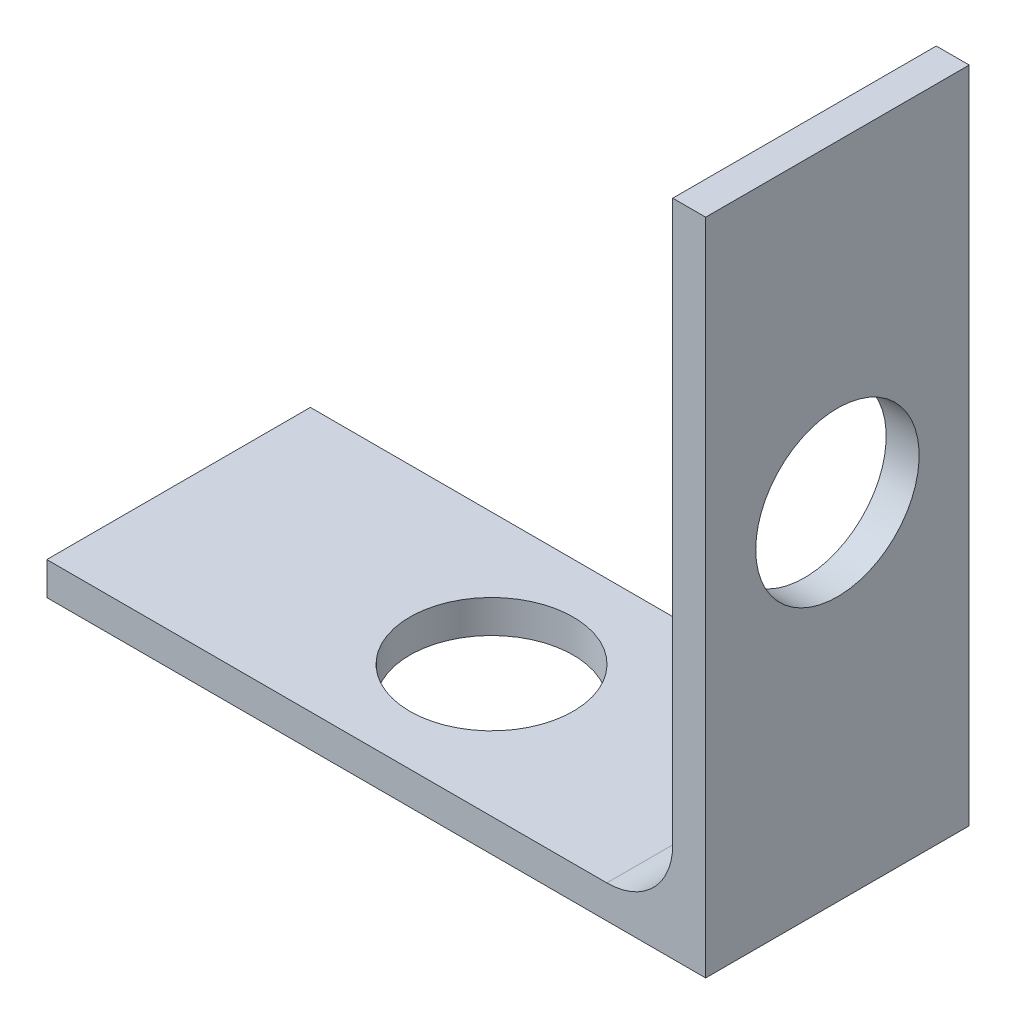
SolidWorks part; units mm, degrees
ref_plane "Front Plane" through (0, 0, 0) normal (0, 0, 1) x (1, 0, 0)
ref_plane "Top Plane" through (0, 0, 0) normal (0, 1, 0) x (1, 0, 0)
ref_plane "Right Plane" through (0, 0, 0) normal (1, 0, 0) x (0, 0, -1)
sketch "Sketch1" plane through (0, 0, 0) normal (0, 0, 1) x (1, 0, 0)
  line L0 (0, 0) -> (31.75, 0)
  line L1 (31.75, 0) -> (31.75, 31.75)
  line L2 (0, 0) -> (0, 1.5875)
  line L3 (0, 1.5875) -> (30.1625, 1.5875)
  line L4 (30.1625, 1.5875) -> (30.1625, 31.75)
  line L5 (30.1625, 31.75) -> (31.75, 31.75)
  dimension "D1" = 31.75
  dimension "D2" = 31.75
  dimension "D3" = 1.5875
  dimension "D4" = 1.5875
extrude "Boss-Extrude1" add sketch "Sketch1" along normal blind 12.7
sketch "Sketch2" plane through (30.1625, 0, 0) normal (-1, 0, 0) x (0, 0, 1)
  line L0 (6.35, 31.75) -> (6.35, 1.5875) construction
  line L1 (12.7, 31.75) -> (0, 31.75) construction
  line L2 (12.7, 1.5875) -> (0, 1.5875) construction
  line L3 (0, 16.6687) -> (12.7, 16.6687) construction
  line L4 (0, 31.75) -> (0, 1.5875) construction
  line L5 (12.7, 31.75) -> (12.7, 1.5875) construction
  circle A0 centre (6.35, 16.6687) radius 3.937
  dimension "D1" = 7.874
extrude "Cut-Extrude1" cut sketch "Sketch2" against normal blind 6.35
sketch "Sketch4" plane through (0, 1.5875, 0) normal (0, 1, 0) x (1, 0, 0)
  line L0 (15.0813, 0) -> (15.0813, -12.7) construction
  line L1 (30.1625, 0) -> (0, 0) construction
  line L2 (30.1625, -12.7) -> (0, -12.7) construction
  line L3 (0, -6.35) -> (30.1625, -6.35) construction
  line L4 (0, -12.7) -> (0, 0) construction
  line L5 (30.1625, -12.7) -> (30.1625, 0) construction
  circle A0 centre (15.0813, -6.35) radius 3.937
  dimension "D1" = 7.874
extrude "Cut-Extrude2" cut sketch "Sketch4" against normal blind 6.35
fillet "Fillet2" radius 3.175 1 edges at (30.1625, 1.5875, 6.35) type face fillet first side face at (30.1625, 16.6687, 10.287) second side face at (15.0813, 1.5875, 10.287)
